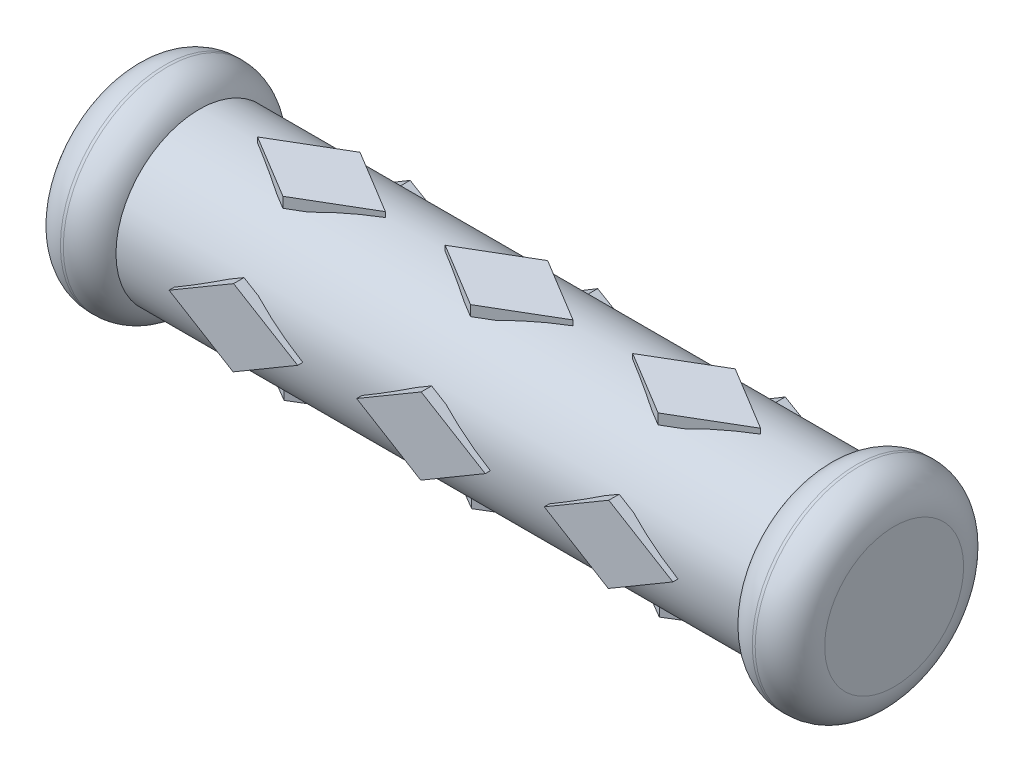
SolidWorks part; units mm, degrees
material "VITON"
ref_plane "Alzado" through (0, 0, 0) normal (0, 0, 1) x (1, 0, 0)
ref_plane "Planta" through (0, 0, 0) normal (0, 1, 0) x (1, 0, 0)
ref_plane "Vista lateral" through (0, 0, 0) normal (1, 0, 0) x (0, 0, -1)
sketch "Croquis1" plane through (0, 0, 0) normal (1, 0, 0) x (0, 0, -1)
  circle A0 centre (0, 0) radius 12
  dimension "D1" = 24
extrude "Saliente-Extruir1" add sketch "Croquis1" along normal blind 110
sketch "Croquis3" plane through (110, 0, 0) normal (1, 0, 0) x (0, 0, -1)
  circle A0 centre (0, 0) radius 11
  dimension "D1" = 22
extrude "Cortar-Extruir1" cut sketch "Croquis3" against normal blind 110
sketch "Croquis4" plane through (110, 0, 0) normal (1, 0, 0) x (0, 0, -1)
  circle A0 centre (0, 0) radius 15
  dimension "D1" = 30
extrude "Saliente-Extruir3" add sketch "Croquis4" against normal blind 10
fillet "Redondeo1" radius 5 2 edges at (110, 0, -15) (100, 0, -15)
sketch "Croquis5" plane through (0, 0, 0) normal (-1, 0, 0) x (0, 0, 1)
  circle A0 centre (0, 0) radius 15
  dimension "D1" = 30
extrude "Saliente-Extruir4" add sketch "Croquis5" against normal blind 10
fillet "Redondeo2" radius 5 2 edges at (10, 0, 15) (0, 0, 15)
sketch "Croquis7" plane through (0, 0, 0) normal (-1, 0, 0) x (0, 0, 1)
  circle A0 centre (0, 0) radius 11
  dimension "D1" = 22
extrude "Cortar-Extruir2" cut sketch "Croquis7" against normal blind 100
sketch3d "Croquis3D1"
  point P0 (41.8594, 0.5996, 11.985)
ref_plane "Plano1" through (0, 0, 11.985) normal (0, 0, 1) x (1, 0, 0)
sketch "Croquis9" plane through (0, 0, 11.985) normal (0, 0, 1) x (1, 0, 0)
  line L4 (27.6638, 5.4625) -> (27.6638, -7.0674) construction
  line L5 (18.3752, 0) -> (27.6638, 5.4625)
  line L6 (18.3752, 0) -> (27.5983, -5.5723)
  line L7 (27.6638, 5.4625) -> (36.8869, -0.1098)
  line L8 (27.5983, -5.5723) -> (36.8869, -0.1098)
  line L9 (45.3752, 0) -> (54.6638, 5.4625)
  line L10 (45.3752, 0) -> (54.5983, -5.5723)
  line L11 (54.5983, -5.5723) -> (63.8869, -0.1098)
  line L12 (54.6638, 5.4625) -> (63.8869, -0.1098)
  line L13 (72.3752, 0) -> (81.6638, 5.4625)
  line L14 (72.3752, 0) -> (81.5983, -5.5723)
  line L15 (81.5983, -5.5723) -> (90.8869, -0.1098)
  line L16 (81.6638, 5.4625) -> (90.8869, -0.1098)
  dimension "D1" = 3
extrude "Saliente-Extruir5" add sketch "Croquis9" along normal mid plane 1.5
pattern_circular "MatrizC1" count 4 over 360 about axis through (0, 0, 0) along (1, 0, 0) of "Saliente-Extruir5"
